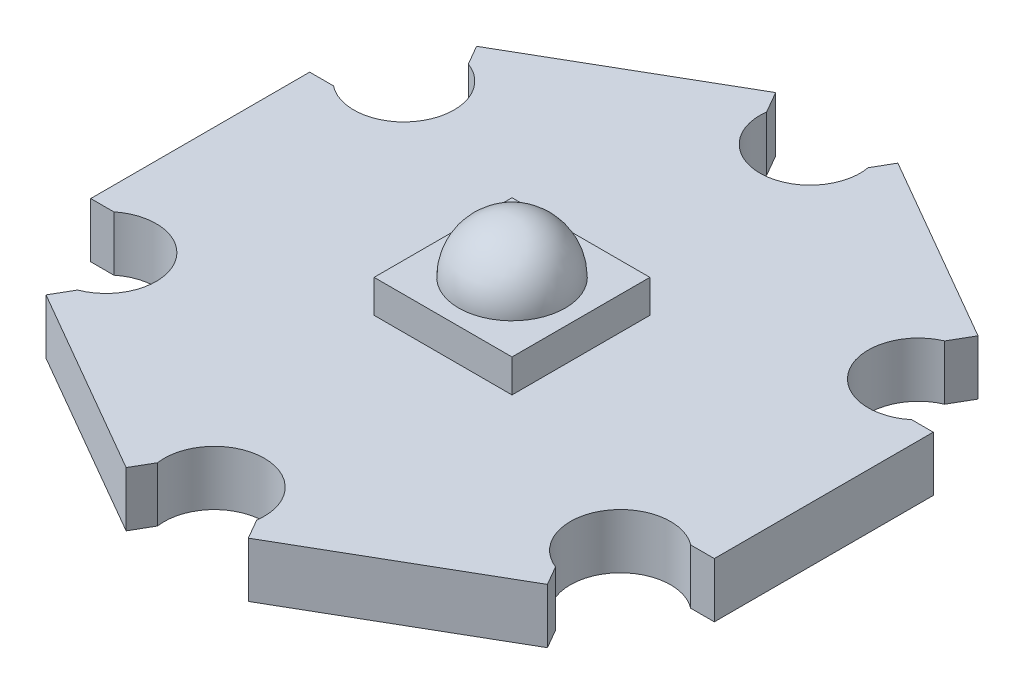
SolidWorks part; units mm, degrees
ref_plane "Front Plane" through (0, 0, 0) normal (0, 0, 1) x (1, 0, 0)
ref_plane "Top Plane" through (0, 0, 0) normal (0, 1, 0) x (1, 0, 0)
ref_plane "Right Plane" through (0, 0, 0) normal (1, 0, 0) x (0, 0, -1)
sketch "Sketch1" plane through (0, 0, 0) normal (0, 1, 0) x (1, 0, 0)
  circle A0 centre (0, 0) radius 9.5
extrude "Boss-Extrude1" add sketch "Sketch1" along normal blind 1.75
sketch "Sketch5" plane through (0, 1.75, 0) normal (0, 1, 0) x (1, 0, 0)
  line L0 (4.7443, -8.2305) -> (-4.7319, 8.2377) construction
  line L1 (-9.5, 0.0066) -> (9.5, -0.021) construction
  line L2 (-8.0004, 6.8702) -> (1.9496, -10.3637)
  line L3 (-9.95, -3.4934) -> (9.95, -3.4934)
  line L4 (-9.95, -3.4934) -> (-9.95, 3.5066)
  line L5 (-9.95, 3.5066) -> (9.95, 3.5066)
  line L6 (9.95, -3.4934) -> (9.95, 3.5066)
  line L7 (-8.0004, 6.8702) -> (-1.9382, 10.3702)
  line L8 (-1.9382, 10.3702) -> (8.0118, -6.8637)
  line L9 (1.9496, -10.3637) -> (8.0118, -6.8637)
  line L10 (-4.7443, 8.2305) -> (4.7318, -8.2377) construction
  line L11 (1.9496, 10.3637) -> (-8.0004, -6.8702)
  line L12 (1.9496, 10.3637) -> (8.0118, 6.8637)
  line L13 (8.0118, 6.8637) -> (-1.9382, -10.3702)
  line L14 (-8.0004, -6.8702) -> (-1.9382, -10.3702)
  line L15 (4.7557, 8.2239) -> (-4.7682, -8.2167) construction
  line L16 (9.95, 3.4934) -> (-9.95, 3.4934)
  line L17 (9.95, 3.4934) -> (9.95, -3.5066)
  line L18 (9.95, -3.5066) -> (-9.95, -3.5066)
  line L19 (-9.95, 3.4934) -> (-9.95, -3.5066)
  line L20 (9.5, -0.0066) -> (-9.5, 0.021) construction
  line L21 (8.0004, -6.8702) -> (-1.9496, 10.3637)
  line L22 (8.0004, -6.8702) -> (1.9382, -10.3702)
  line L23 (1.9382, -10.3702) -> (-8.0118, 6.8637)
  line L24 (-1.9496, 10.3637) -> (-8.0118, 6.8637)
  line L25 (4.7443, -8.2305) -> (-4.7318, 8.2377) construction
  line L26 (-1.9496, -10.3637) -> (8.0004, 6.8702)
  line L27 (-1.9496, -10.3637) -> (-8.0118, -6.8637)
  line L28 (-8.0118, -6.8637) -> (1.9382, 10.3702)
  line L29 (8.0004, 6.8702) -> (1.9382, 10.3702)
  line L30 (-4.7557, -8.2239) -> (4.7682, 8.2167) construction
  circle A0 centre (0, 0) radius 9.5 construction
  circle A1 centre (0, 0) radius 9.5 construction
  circle A2 centre (0, 0) radius 9.5 construction
  circle A3 centre (0, 0) radius 9.5 construction
  point P20 (0, 0)
  point P30 (0, 0)
  point P37 (0, 0)
  point P44 (0, 0)
  point P51 (0, 0)
  point P58 (0, 0)
  point P59 (0, 0)
  circle M6 centre (0, 0) radius 9.5
  circle M8 centre (0, 0) radius 9.5
  circle M10 centre (0, 0) radius 9.5
  circle M12 centre (0, 0) radius 9.5
  circle M14 centre (0, 0) radius 9.5
  circle M16 centre (0, 0) radius 9.5
  dimension "D1" = 19.9
  dimension "D2" = 9.95
  dimension "D3" = 7
  dimension "D4" = 3.5
  dimension "D5" = 6
extrude "Boss-Extrude4" add sketch "Sketch5" against normal blind 1.75 contours L16 L4 L3 M16 | L21 L7 L2 M14 | L26 L12 L11 M12 | L9 L21 L2 M8 | L6 L16 L3 M10 | L14 L26 L11 M6 region at (-4.7933, 1.75, -8.3022) region at (-9.5865, 1.75, 0) region at (4.7933, 1.75, -8.3022) region at (-4.7933, 1.75, 8.3022) region at (9.5865, 1.75, 0) region at (4.7933, 1.75, 8.3022)
sketch "Sketch2" plane through (0, 1.75, 0) normal (0, 1, 0) x (1, 0, 0)
  line L0 (0, 0) -> (0, -19.7205) construction
  circle A0 centre (0, -9.5) radius 1.6
  circle A1 centre (0, 0) radius 9.5 construction
  circle A2 centre (-8.2135, -4.7421) radius 1.6
  circle A3 centre (-8.1997, 4.75) radius 1.6
  circle A4 centre (0.0275, 9.4841) radius 1.6
  circle A5 centre (8.241, 4.7262) radius 1.6
  circle A6 centre (8.2272, -4.7659) radius 1.6
  point P0 (0, 0)
  point P22 (0.0137, -0.008)
  dimension "D1" = 6
  dimension "D2" = 3.2
extrude "Cut-Extrude1" cut sketch "Sketch2" against normal blind 1.75
sketch "Sketch3" plane through (0, 1.75, 0) normal (0, 1, 0) x (1, 0, 0)
  line L0 (-9.5, 0) -> (28.1538, 0) construction
  line L1 (0, 7.8843) -> (0, -19.8144) construction
  line L3 (-2.2, 2.2) -> (2.2, 2.2)
  line L4 (-2.2, 2.2) -> (-2.2, -2.2)
  line L5 (-2.2, -2.2) -> (2.2, -2.2)
  line L6 (2.2, 2.2) -> (2.2, -2.2)
  arc A0 (-8.9036, 3.3131) -> (-8.9081, -3.3007) centre (0, 0) ccw construction
  arc A1 (-1.5595, 9.6879) -> (1.6029, 9.7632) centre (0.0275, 9.4841) ccw construction
  dimension "D1" = 4.4
  dimension "D2" = 4.4
  dimension "D3" = 2.2
  dimension "D4" = 2.2
extrude "Boss-Extrude2" add sketch "Sketch3" along normal blind 1.05
sketch "Sketch4" plane through (0, 2.8, 0) normal (0, 1, 0) x (1, 0, 0)
  circle A0 centre (0, 0) radius 1.7
extrude "Boss-Extrude3" add sketch "Sketch4" along normal blind 1.7
fillet "Fillet1" radius 1.7 1 edges at (0, 4.5, 1.7)
sketch "Sketch6" plane through (0, 1.75, 0) normal (0, 1, 0) x (1, 0, 0)
  line L0 (-7.1443, -7.3645) -> (-10.8348, -5.2338) construction
  line L1 (-8.0004, -6.8702) -> (-1.9496, -10.3637) construction
  line L2 (-9.95, -2.652) -> (-9.95, -7.6957) construction
  line L3 (-9.95, -3.4934) -> (-9.95, 3.4934) construction
  circle A0 centre (0, 0) radius 11.4893
  point P8 (-9.95, -5.7446)
